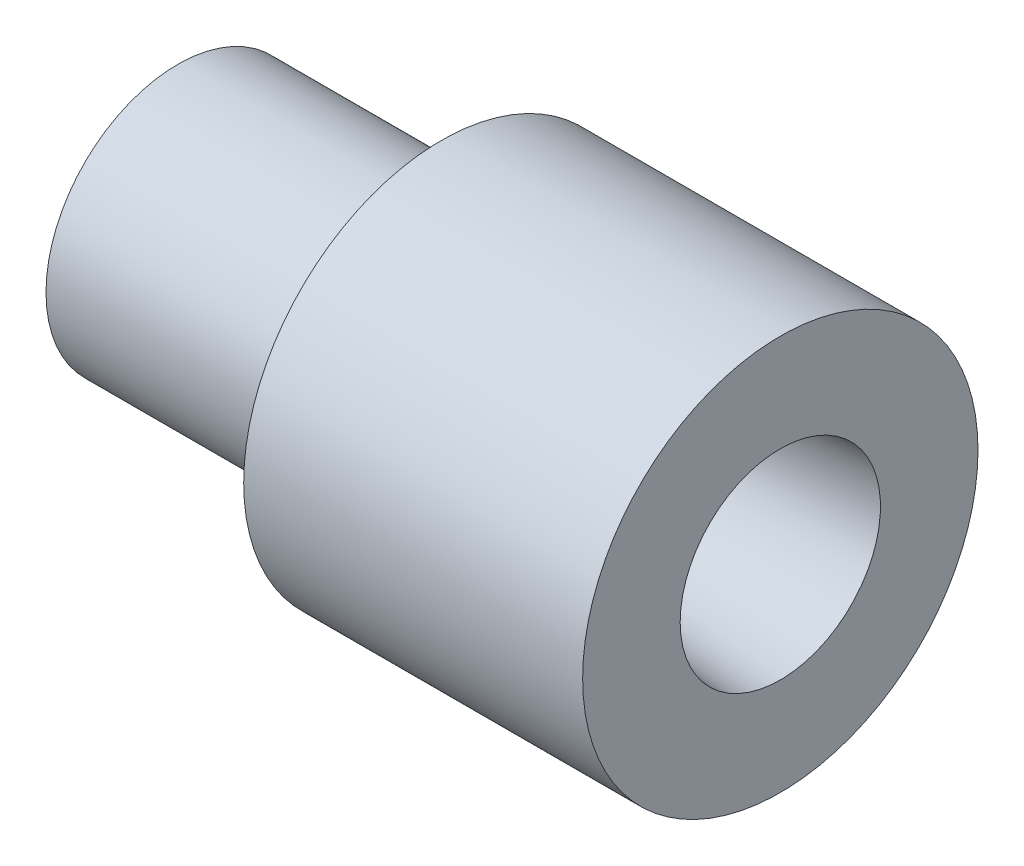
SolidWorks part; units mm, degrees
ref_plane "Front Plane" through (0, 0, 0) normal (0, 0, 1) x (1, 0, 0)
ref_plane "Top Plane" through (0, 0, 0) normal (0, 1, 0) x (1, 0, 0)
ref_plane "Right Plane" through (0, 0, 0) normal (1, 0, 0) x (0, 0, -1)
sketch "Sketch1" plane through (0, 0, 0) normal (0, 1, 0) x (1, 0, 0)
  line L0 (0, 0) -> (0, 2.286) construction
  line L1 (0, 2.286) -> (0, 6.35)
  line L2 (12.7, 9.525) -> (29.0323, 9.525)
  line L3 (29.0323, 9.525) -> (29.0323, 4.826)
  line L4 (29.0323, 4.826) -> (0, 2.286)
  line L5 (0, 0) -> (29.0323, 0) construction
  line L6 (29.0323, 0) -> (29.0323, 4.826) construction
  line L8 (12.7, 6.35) -> (12.7, 9.525)
  line L12 (0, 6.35) -> (12.7, 6.35)
  dimension "D1" = 2.286
  dimension "D2" = 4.826
  dimension "D3" = 5
  dimension "D4" = 9.525
  dimension "D5" = 6.35
  dimension "D6" = 12.7
revolve "Revolve1" add sketch "Sketch1" angle 360 about L5
equation "\"z\" = 8\t\t\t\t'number of blades"
equation "\"de\" = 0.43in\t\t\t'entrance eye diameter"
equation "\"de_length\" = 10mm\t\t'entrance eye consistent length"
equation "\"d_exit\" = 0.18in \t\t'throat aka d1"
equation "\"d2\" = 2.1in \t\t\t'outer diameter of the impeller"
equation "\"b2\" = .2in\t\t\t'tip height from disc surface at d2; slightly higher than d_exit"
equation "\"b1\" = \"b2\" + (\"d2\"/2 - \"de\"/2)*tan(\"theta\") \t\t\t'tip height from disc surface at inlet eye"
equation "\"theta\" = 12\t\t\t'angle of blades from inner to outer "
equation "\"ae\" = 3.14*(\"de\"^2)/4\t\t'entrance eye area'"
equation "\"ce\" = 3.14*\"de\"\t\t'entrance eye circumference"
equation "\"av_ratio\" = .325\t\t'ratio of av/ae at N_s of 470, range is .275 to .375, .325 ideal. High ratio means bigger area means smaller blades"
equation "\"av\" = \"ae\"*\"av_ratio\"\t\t'area between just two blades"
equation "\"s_open\" = \"av\"/\"b1\"\t\t'width of open area"
equation "\"s\"=\"ce\" - \"z\"*\"s_open\""
equation "\"min blade thickness\" = .15in"
equation "\"bearing OD\" = 30mm"
equation "\"bearing ID\"= 10mm"
equation "\"bearing depth\"= 9mm"
equation "\"bearing outer race thickness\"= 1mm"
equation "\"bearing inner race thickness\"= 1mm"
equation "\"bearing bore\" = \"bearing depth\" + 1mm"
equation "\"lower seal OD\" = .917in\t\t'this is https://www.mcmaster.com/#9281k121/=174001b"
equation "\"lower seal ID\"= .375in"
equation "\"lower seal depth\" = .625in + .218in"
equation "\"lower seal bore\" = \"lower seal depth\" + 1mm"
equation "\"upper seal OD\" = 1.125in\t'this is https://www.mcmaster.com/#5154t33/=173zuau, needs to be visually inspected before machining!"
equation "\"upper seal ID\"= 0.625in"
equation "\"upper seal depth\"= .25in\t'aka height; these values need to be confirmed by inspection!! We may want to compress the height."
equation "\"upper seal bore\" = \"upper seal depth\" + 1mm"
equation "\"big o-ring thickness\" = .139in"
equation "\"big o-ring OD\" = 2.734in"
equation "\"big o-ring ID\" = 3.012in"
equation "\"big o-ring groove depth\" = \"big o-ring thickness\"*4/5"
equation "\"impeller center height\" = \"impeller base thickness\" + \"b1\"\t'impeller height at de"
equation "\"impeller outer height\" = \"impeller base thickness\" + \"b2\"\t'impeller height at de"
equation "\"impeller upper clearance\"= .5mm"
equation "\"impeller horizontal clearance\"= (\"d2\"*1.15 - \"d2\")/2 \t\t'clearance based on D2-D3 ratio for circular volute, ranges 1.15 to 1.2"
equation "\"impeller bottom clearance\"= .5mm"
equation "\"impeller base thickness\"= 2mm"
equation "\"impeller dowel diameter\" = 2mm"
equation "\"impeller bolt head diameter\" = \"m4 head bore diameter\""
equation "\"impeller bolt head depth\" = 4mm"
equation "\"impeller bolt stop depth\" = 3mm"
equation "\"impeller bolt bore\" = \"m4 clearance\""
equation "\"impeller shaft bore depth\" = 12mm"
equation "\"impeller shaft bore\" = 8mm"
equation "\"impeller boss depth\" = \"impeller shaft bore depth\"+\"impeller bolt stop depth\"+\"impeller bolt head depth\"-\"impeller base thickness\""
equation "\"impeller boss diameter\" = \"upper seal ID\""
equation "\"impeller dowel length\" = 2mm*2 + \"impeller shaft bore\""
equation "\"coupler motor shaft hole ID\"= 8mm"
equation "\"coupler OD\"= 17mm"
equation "\"coupler length\"= 25mm"
equation "\"motor OD\" = 64mm"
equation "\"motor shaft diameter\"= 8mm"
equation "\"motor shaft pride\"= 32mm"
equation "\"motor to bearing plate distance\" = \"motor shaft pride\" + 2mm +\"coupler length\"/2"
equation "\"square plate bolt bore\" = \"m8 clearance\""
equation "\"square plate bolt head diameter\" = 13.5mm"
equation "\"square plate bolt head depth\" = 8mm"
equation "\"square plate bolt pattern diameter\"= 3.5in"
equation "\"motor mount center bore\"= \"coupler OD\"+ 4mm"
equation "\"motor mount post radius\"= ( 3 * \"square plate bolt bore\" ) / 2"
equation "\"motor mount m4 screw hole diameter\"= 4mm"
equation "\"motor mount m4 head diameter\"= 7.25mm"
equation "\"motor mount m4 head depth\"= 4mm"
equation "\"motor mount m4 pattern diamater\" = 30mm"
equation "\"motor mount plate thickness\"= 8mm + \"motor mount m4 head depth\""
equation "\"bearing plate stop ID\" = \"bearing OD\" - 4mm"
equation "\"bearing plate stop depth\" = 3mm"
equation "\"bearing plate thickness\" = \"bearing bore\" + \"bearing plate stop depth\" + \"shaft bearing stop length\""
equation "\"lower seal plate lip depth\" = 2mm"
equation "\"lower seal plate lip ID\" = \"lower seal OD\" - 3mm"
equation "\"lower seal plate thickness\" = \"lower seal plate lip depth\" + \"lower seal bore\""
equation "\"shaft coupler section diameter\" = 8mm"
equation "\"shaft coupler section length\" = \"motor to bearing plate distance\" - \"motor shaft pride\" - 2mm"
equation "\"shaft bearing section diameter\" = \"bearing ID\""
equation "\"shaft bearing section length\" = \"bearing plate stop depth\" + \"bearing depth\""
equation "\"shaft bearing stop diameter\" = \"bearing ID\" + 4mm"
equation "\"shaft bearing stop length\" = 3mm"
equation "\"shaft lower seal section diameter\" = \"lower seal ID\""
equation "\"shaft lower seal section length\" = \"lower seal plate thickness\" + 1mm"
equation "\"shaft impeller section diameter\" = \"impeller shaft bore\""
equation "\"shaft impeller section length\" = \"upper seal plate thickness\" + \"upper seal plate riser\" + \"impeller bottom clearance\" + \"impeller base thickness\" - \"impeller bolt head depth\" - \"impeller bolt stop depth\""
equation "\"upper seal plate thickness\" = \"upper seal plate pressure hole diameter\"+10mm"
equation "\"upper seal plate lip ID\" = \"upper seal OD\" - 3mm"
equation "\"upper seal plate riser\" = 6.59mm \t\t'this number needs to be read from the housing file"
equation "\"upper seal plate pressure hole diameter\" = .125in\t'this is 1/8 drill "
equation "\"upper seal plate pressure tap diameter\" = .328125in \t'this is 21/64 drill for a 1/8 ANPT tap"
equation "\"upper seal plate pressure tap grip\" = 5mm\t\t'this is the area around the tap so it doesn't crack"
equation "\"upper seal plate pressure tap depth\" = 12"
equation "\"impeller cavity center height\"= \"impeller bottom clearance\" + \"impeller upper clearance\" + \"impeller center height\""
equation "\"impeller cavity diameter\"= 2 * \"impeller horizontal clearance\" + \"d2\" \t\t\t\t\t\t\t\t\t'called D3 analytically"
equation "\"impeller cavity outer height\"= \"impeller bottom clearance\" + \"impeller upper clearance\" + \"impeller base thickness\" + \"b2\" \t\t'this is height at impeller diameter d2, not at d3"
equation "\"impeller housing thickness\"= \"impeller housing exit threaded diameter\" + 2*\"impeller housing outlet grip\""
equation "\"impeller housing diameter\" = \"square plate bolt pattern diameter\" + 2*\"motor mount post radius\""
equation "\"impeller housing bolt count\" = 8"
equation "\"impeller housing bolt diameter\" = \"m6 clearance\""
equation "\"impeller housing bolt pattern diameter\" = 3.5in"
equation "\"impeller housing threaded inlet diameter\" = 0.515625in \t'this is the 33/64 drill size for 9/16-18 fitting, expecting swagelok SS-8FK0-1-6STH fitting"
equation "\"impeller housing threaded inlet depth\"= 10mm"
equation "\"impeller housing exit threaded diameter\"= 0.515625in \t\t'this is the 33/64 drill size for 9/16-18 fitting, expecting swagelok SS-8FK0-1-6STH fitting"
equation "\"impeller housing exit threaded depth\"= 10mm"
equation "\"impeller housing diffuser conical angle\"=10"
equation "\"impeller housing diffuser tangent angle\"=5"
equation "\"impeller housing diffuser final diameter\" = .38in\t\t'aka d2'"
equation "\"impeller housing outlet grip\" = 5mm"
equation "\"end mill size\" = 0.375in\t'for 3/8 endmill"
equation "\"m4 clearance\" = 0.171875in \t'this is 11/64 bit for 4.36mm"
equation "\"m4 tap\" = 0.125in\t\t'this is 1/8 bit for 3.17mm"
equation "\"m4 head bore diameter\" = 7.5mm"
equation "\"m4 head bore depth\" = 5mm\t'actual is ~4mm"
equation "\"m6 clearance\" = 0.234375in\t'this is 15/64 bit = 5.95mm, could use 6mm bit, B bit for 6.04mm or 1/4 bit for 6.35mm"
equation "\"m6 tap\" = 5mm\t\t\t'5mm is appropriate, could use 13/64 or #5,6,7"
equation "\"m6 head bore diameter\" = 11mm\t\t"
equation "\"m6 head bore depth\" = 7mm\t'actual is 6mm"
equation "\"m8 clearance\" = 0.3125in\t'this is 5/16in for 7.93mm, could use 8mm, O,P, or 21/64"
equation "\"m8 tap\" = 0.265625in\t\t'this is 17/64 for 6.746875mm"
equation "\"m8 head bore diameter\" = 14mm"
equation "\"m8 head bore depth\" = 9mm\t'actual is 8mm"
equation "\"D1@Sketch1\"=\"d_exit\"/2"
equation "\"D2@Sketch1\"=\"impeller housing diffuser final diameter\"/2"
equation "\"diffuser cartridge OD\" =.75in"
equation "\"D4@Sketch1\"=\"diffuser cartridge OD\"/2"
